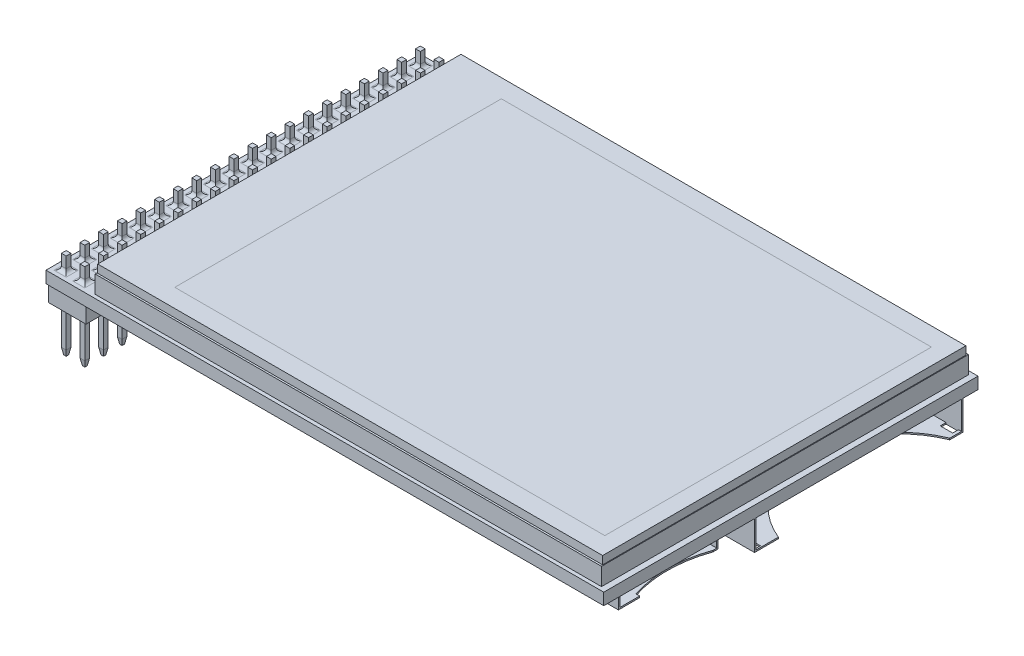
SolidWorks part; units mm, degrees
ref_plane "Спереди" through (0, 0, 0) normal (0, 0, 1) x (1, 0, 0)
ref_plane "Сверху" through (0, 0, 0) normal (0, 1, 0) x (1, 0, 0)
ref_plane "Справа" through (0, 0, 0) normal (1, 0, 0) x (0, 0, -1)
sketch "Эскиз10" plane through (0, 0, 0) normal (0, 1, 0) x (1, 0, 0)
  line L0 (278.9333, -1.3667) -> (1412.2667, -1.3667) construction
sketch "Эскиз1" plane through (0, 0, 0) normal (0, 1, 0) x (1, 0, 0)
  line L1 (0, -25.5) -> (76, -25.5)
  line L2 (0, -25.5) -> (0, 25.5)
  line L3 (0, 25.5) -> (76, 25.5)
  line L4 (76, -25.5) -> (76, 25.5)
  dimension "D1" = 51
  dimension "D2" = 76
extrude "Бобышка-Вытянуть1" add sketch "Эскиз1" along normal blind 1.6
sketch "Эскиз2" plane through (0, 0, 0) normal (0, -1, 0) x (1, 0, 0)
  line L0 (0, 0) -> (0.1, 0) construction
  line L1 (0.1, -25.25) -> (5.2, -25.25)
  line L2 (0.1, -25.25) -> (0.1, 25.25)
  line L3 (0.1, 25.25) -> (5.2, 25.25)
  line L4 (5.2, -25.25) -> (5.2, 25.25)
  dimension "D1" = 0.1
  dimension "D2" = 50.5
  dimension "D3" = 5.1
extrude "Бобышка-Вытянуть2" add sketch "Эскиз2" along normal blind 2.3
sketch "Эскиз3" plane through (0, -2.3, 0) normal (0, -1, 0) x (1, 0, 0)
  line L0 (1.38, -24.13) -> (1.38, -21.59) construction
  line L1 (1.38, -21.59) -> (1.38, -19.05) construction
  line L2 (1.38, -19.05) -> (1.38, -16.51) construction
  line L3 (1.38, -16.51) -> (1.38, -13.97) construction
  line L4 (1.38, -13.97) -> (1.38, -11.43) construction
  line L5 (1.38, -11.43) -> (1.38, -8.89) construction
  line L6 (1.38, -8.89) -> (1.38, -6.35) construction
  line L7 (1.38, -6.35) -> (1.38, -3.81) construction
  line L8 (1.38, -3.81) -> (1.38, -1.27) construction
  line L9 (1.38, -1.27) -> (1.38, 1.27) construction
  line L10 (1.38, 1.27) -> (1.38, 3.81) construction
  line L11 (1.38, 3.81) -> (1.38, 6.35) construction
  line L12 (1.38, 6.35) -> (1.38, 8.89) construction
  line L13 (1.38, 8.89) -> (1.38, 11.43) construction
  line L14 (1.38, 11.43) -> (1.38, 13.97) construction
  line L15 (1.38, 13.97) -> (1.38, 16.51) construction
  line L16 (1.38, 16.51) -> (1.38, 19.05) construction
  line L17 (1.38, 19.05) -> (1.38, 21.59) construction
  line L18 (1.38, 21.59) -> (1.38, 24.13) construction
  line L19 (1.38, 24.13) -> (3.92, 24.13) construction
  line L20 (3.92, 24.13) -> (3.92, 21.59) construction
  line L21 (3.92, 21.59) -> (1.38, 21.59) construction
  line L22 (3.92, 21.59) -> (3.92, 19.05) construction
  line L23 (3.92, 19.05) -> (1.38, 19.05) construction
  line L24 (3.92, 19.05) -> (3.92, 16.51) construction
  line L25 (3.92, 16.51) -> (1.38, 16.51) construction
  line L26 (3.92, 16.51) -> (3.92, 13.97) construction
  line L27 (3.92, 13.97) -> (1.38, 13.97) construction
  line L28 (3.92, 13.97) -> (3.92, 11.43) construction
  line L29 (3.92, 11.43) -> (1.38, 11.43) construction
  line L30 (3.92, 11.43) -> (3.92, 8.89) construction
  line L31 (3.92, 8.89) -> (1.38, 8.89) construction
  line L32 (3.92, 8.89) -> (3.92, 6.35) construction
  line L33 (3.92, 6.35) -> (1.38, 6.35) construction
  line L34 (3.92, 6.35) -> (3.92, 3.81) construction
  line L35 (3.92, 3.81) -> (1.38, 3.81) construction
  line L36 (3.92, 3.81) -> (3.92, 1.27) construction
  line L37 (3.92, 1.27) -> (1.38, 1.27) construction
  line L38 (3.92, 1.27) -> (3.92, -1.27) construction
  line L39 (3.92, -1.27) -> (1.38, -1.27) construction
  line L40 (3.92, -1.27) -> (3.92, -3.81) construction
  line L41 (3.92, -3.81) -> (1.38, -3.81) construction
  line L42 (3.92, -3.81) -> (3.92, -6.35) construction
  line L43 (3.92, -6.35) -> (1.38, -6.35) construction
  line L44 (3.92, -6.35) -> (3.92, -8.89) construction
  line L45 (3.92, -8.89) -> (1.38, -8.89) construction
  line L46 (3.92, -8.89) -> (3.92, -11.43) construction
  line L47 (3.92, -11.43) -> (1.38, -11.43) construction
  line L48 (3.92, -11.43) -> (3.92, -13.97) construction
  line L49 (3.92, -13.97) -> (1.38, -13.97) construction
  line L50 (3.92, -13.97) -> (3.92, -16.51) construction
  line L51 (3.92, -16.51) -> (1.38, -16.51) construction
  line L52 (3.92, -16.51) -> (3.92, -19.05) construction
  line L53 (3.92, -19.05) -> (1.38, -19.05) construction
  line L54 (3.92, -19.05) -> (3.92, -21.59) construction
  line L55 (3.92, -21.59) -> (1.38, -21.59) construction
  line L56 (3.92, -21.59) -> (3.92, -24.13) construction
  line L57 (3.92, -24.13) -> (1.38, -24.13) construction
  line L58 (1.38, 0) -> (0.1, 0) construction
  line L59 (0.1, 25.25) -> (0.1, -25.25) construction
  line L60 (2.65, 25.25) -> (2.65, 24.13) construction
  line L61 (5.2, 25.25) -> (0.1, 25.25) construction
  line L62 (1.705, 23.805) -> (1.055, 24.455) construction
  line L63 (1.055, 24.455) -> (1.705, 24.455)
  line L64 (1.055, 24.455) -> (1.055, 23.805)
  line L65 (1.055, 23.805) -> (1.705, 23.805)
  line L66 (1.705, 24.455) -> (1.705, 23.805)
  line L67 (1.055, 21.915) -> (1.705, 21.915)
  line L68 (1.055, 21.915) -> (1.055, 21.265)
  line L69 (1.055, 21.265) -> (1.705, 21.265)
  line L70 (1.705, 21.915) -> (1.705, 21.265)
  line L71 (1.055, 21.915) -> (1.705, 21.265) construction
  line L72 (1.055, 19.375) -> (1.705, 18.725) construction
  line L73 (1.055, 1.595) -> (1.705, 0.945) construction
  line L74 (1.055, 1.595) -> (1.705, 1.595)
  line L75 (1.055, 1.595) -> (1.055, 0.945)
  line L76 (1.055, 0.945) -> (1.705, 0.945)
  line L77 (1.705, 1.595) -> (1.705, 0.945)
  line L78 (1.055, -0.945) -> (1.705, -1.595) construction
  line L79 (1.055, 16.835) -> (1.705, 16.185) construction
  line L80 (1.055, 4.135) -> (1.705, 4.135)
  line L81 (1.055, 4.135) -> (1.055, 3.485)
  line L82 (1.055, 3.485) -> (1.705, 3.485)
  line L83 (1.705, 4.135) -> (1.705, 3.485)
  line L84 (1.055, 6.675) -> (1.705, 6.675)
  line L85 (1.055, 6.675) -> (1.055, 6.025)
  line L86 (1.055, 6.025) -> (1.705, 6.025)
  line L87 (1.705, 6.675) -> (1.705, 6.025)
  line L88 (1.055, 9.215) -> (1.705, 9.215)
  line L89 (1.055, 9.215) -> (1.055, 8.565)
  line L90 (1.055, 8.565) -> (1.705, 8.565)
  line L91 (1.705, 9.215) -> (1.705, 8.565)
  line L92 (1.055, 11.755) -> (1.705, 11.755)
  line L93 (1.055, 11.755) -> (1.055, 11.105)
  line L94 (1.055, 11.105) -> (1.705, 11.105)
  line L95 (1.705, 11.755) -> (1.705, 11.105)
  line L96 (1.055, 14.295) -> (1.705, 14.295)
  line L97 (1.055, 14.295) -> (1.055, 13.645)
  line L98 (1.055, 13.645) -> (1.705, 13.645)
  line L99 (1.705, 14.295) -> (1.705, 13.645)
  line L100 (1.055, 16.835) -> (1.705, 16.835)
  line L101 (1.055, 16.835) -> (1.055, 16.185)
  line L102 (1.055, 16.185) -> (1.705, 16.185)
  line L103 (1.705, 16.835) -> (1.705, 16.185)
  line L104 (1.055, 19.375) -> (1.705, 19.375)
  line L105 (1.055, 19.375) -> (1.055, 18.725)
  line L106 (1.055, 18.725) -> (1.705, 18.725)
  line L107 (1.705, 19.375) -> (1.705, 18.725)
  line L108 (1.055, 14.295) -> (1.705, 13.645) construction
  line L109 (1.055, 11.755) -> (1.705, 11.105) construction
  line L110 (1.055, -0.945) -> (1.705, -0.945)
  line L111 (1.055, 9.215) -> (1.705, 8.565) construction
  line L112 (1.055, 6.675) -> (1.705, 6.025) construction
  line L113 (1.055, 4.135) -> (1.705, 3.485) construction
  line L114 (1.055, -0.945) -> (1.055, -1.595)
  line L115 (1.055, -1.595) -> (1.705, -1.595)
  line L116 (1.705, -0.945) -> (1.705, -1.595)
  line L117 (1.055, -3.485) -> (1.705, -3.485)
  line L118 (1.055, -3.485) -> (1.055, -4.135)
  line L119 (1.055, -4.135) -> (1.705, -4.135)
  line L120 (1.705, -3.485) -> (1.705, -4.135)
  line L121 (1.055, -6.025) -> (1.705, -6.025)
  line L122 (1.055, -6.025) -> (1.055, -6.675)
  line L123 (1.055, -6.675) -> (1.705, -6.675)
  line L124 (1.705, -6.025) -> (1.705, -6.675)
  line L125 (1.055, -8.565) -> (1.705, -8.565)
  line L126 (1.055, -8.565) -> (1.055, -9.215)
  line L127 (1.055, -9.215) -> (1.705, -9.215)
  line L128 (1.705, -8.565) -> (1.705, -9.215)
  line L129 (1.055, -11.105) -> (1.705, -11.105)
  line L130 (1.055, -11.105) -> (1.055, -11.755)
  line L131 (1.055, -11.755) -> (1.705, -11.755)
  line L132 (1.705, -11.105) -> (1.705, -11.755)
  line L133 (1.055, -13.645) -> (1.705, -13.645)
  line L134 (1.055, -13.645) -> (1.055, -14.295)
  line L135 (1.055, -14.295) -> (1.705, -14.295)
  line L136 (1.705, -13.645) -> (1.705, -14.295)
  line L137 (1.055, -16.185) -> (1.705, -16.185)
  line L138 (1.055, -16.185) -> (1.055, -16.835)
  line L139 (1.055, -16.835) -> (1.705, -16.835)
  line L140 (1.705, -16.185) -> (1.705, -16.835)
  line L141 (1.055, -18.725) -> (1.705, -18.725)
  line L142 (1.055, -18.725) -> (1.055, -19.375)
  line L143 (1.055, -19.375) -> (1.705, -19.375)
  line L144 (1.705, -18.725) -> (1.705, -19.375)
  line L145 (1.055, -21.265) -> (1.705, -21.265)
  line L146 (1.055, -21.265) -> (1.055, -21.915)
  line L147 (1.055, -21.915) -> (1.705, -21.915)
  line L148 (1.705, -21.265) -> (1.705, -21.915)
  line L149 (1.055, -23.805) -> (1.705, -23.805)
  line L150 (1.055, -23.805) -> (1.055, -24.455)
  line L151 (1.055, -24.455) -> (1.705, -24.455)
  line L152 (1.705, -23.805) -> (1.705, -24.455)
  line L153 (1.055, -3.485) -> (1.705, -4.135) construction
  line L154 (1.055, -6.025) -> (1.705, -6.675) construction
  line L155 (1.055, -8.565) -> (1.705, -9.215) construction
  line L156 (1.055, -11.105) -> (1.705, -11.755) construction
  line L157 (1.055, -13.645) -> (1.705, -14.295) construction
  line L158 (1.055, -16.185) -> (1.705, -16.835) construction
  line L159 (1.055, -18.725) -> (1.705, -19.375) construction
  line L160 (1.055, -21.265) -> (1.705, -21.915) construction
  line L161 (1.055, -23.805) -> (1.705, -24.455) construction
  line L162 (3.595, 23.805) -> (4.245, 24.455) construction
  line L163 (3.595, 24.455) -> (4.245, 24.455)
  line L164 (3.595, 24.455) -> (3.595, 23.805)
  line L165 (3.595, 23.805) -> (4.245, 23.805)
  line L166 (4.245, 24.455) -> (4.245, 23.805)
  line L167 (3.595, 21.265) -> (4.245, 21.915) construction
  line L168 (3.595, 21.915) -> (4.245, 21.915)
  line L169 (3.595, 21.915) -> (3.595, 21.265)
  line L170 (3.595, 21.265) -> (4.245, 21.265)
  line L171 (4.245, 21.915) -> (4.245, 21.265)
  line L172 (3.595, 18.725) -> (4.245, 19.375) construction
  line L173 (3.595, 18.725) -> (4.245, 18.725)
  line L174 (3.595, 18.725) -> (3.595, 19.375)
  line L175 (3.595, 19.375) -> (4.245, 19.375)
  line L176 (4.245, 18.725) -> (4.245, 19.375)
  line L177 (3.595, 16.835) -> (4.245, 16.835)
  line L178 (3.595, 16.835) -> (3.595, 16.185)
  line L179 (3.595, 16.185) -> (4.245, 16.185)
  line L180 (4.245, 16.835) -> (4.245, 16.185)
  line L181 (3.595, 14.295) -> (4.245, 14.295)
  line L182 (3.595, 14.295) -> (3.595, 13.645)
  line L183 (3.595, 13.645) -> (4.245, 13.645)
  line L184 (4.245, 14.295) -> (4.245, 13.645)
  line L185 (3.595, 11.755) -> (4.245, 11.755)
  line L186 (3.595, 11.755) -> (3.595, 11.105)
  line L187 (3.595, 11.105) -> (4.245, 11.105)
  line L188 (4.245, 11.755) -> (4.245, 11.105)
  line L189 (3.595, 9.215) -> (4.245, 9.215)
  line L190 (3.595, 9.215) -> (3.595, 8.565)
  line L191 (3.595, 8.565) -> (4.245, 8.565)
  line L192 (4.245, 9.215) -> (4.245, 8.565)
  line L193 (3.595, 6.675) -> (4.245, 6.675)
  line L194 (3.595, 6.675) -> (3.595, 6.025)
  line L195 (3.595, 6.025) -> (4.245, 6.025)
  line L196 (4.245, 6.675) -> (4.245, 6.025)
  line L197 (3.595, 4.135) -> (4.245, 4.135)
  line L198 (3.595, 4.135) -> (3.595, 3.485)
  line L199 (3.595, 3.485) -> (4.245, 3.485)
  line L200 (4.245, 4.135) -> (4.245, 3.485)
  line L201 (3.595, 1.595) -> (4.245, 1.595)
  line L202 (3.595, 1.595) -> (3.595, 0.945)
  line L203 (3.595, 0.945) -> (4.245, 0.945)
  line L204 (4.245, 1.595) -> (4.245, 0.945)
  line L205 (3.595, -0.945) -> (4.245, -0.945)
  line L206 (3.595, -0.945) -> (3.595, -1.595)
  line L207 (3.595, -1.595) -> (4.245, -1.595)
  line L208 (4.245, -0.945) -> (4.245, -1.595)
  line L209 (3.595, -3.485) -> (4.245, -3.485)
  line L210 (3.595, -3.485) -> (3.595, -4.135)
  line L211 (3.595, -4.135) -> (4.245, -4.135)
  line L212 (4.245, -3.485) -> (4.245, -4.135)
  line L213 (3.595, -6.025) -> (4.245, -6.025)
  line L214 (3.595, -6.025) -> (3.595, -6.675)
  line L215 (3.595, -6.675) -> (4.245, -6.675)
  line L216 (4.245, -6.025) -> (4.245, -6.675)
  line L217 (3.595, -8.565) -> (4.245, -8.565)
  line L218 (3.595, -8.565) -> (3.595, -9.215)
  line L219 (3.595, -9.215) -> (4.245, -9.215)
  line L220 (4.245, -8.565) -> (4.245, -9.215)
  line L221 (3.595, -11.105) -> (4.245, -11.105)
  line L222 (3.595, -11.105) -> (3.595, -11.755)
  line L223 (3.595, -11.755) -> (4.245, -11.755)
  line L224 (4.245, -11.105) -> (4.245, -11.755)
  line L225 (3.595, -13.645) -> (4.245, -13.645)
  line L226 (3.595, -13.645) -> (3.595, -14.295)
  line L227 (3.595, -14.295) -> (4.245, -14.295)
  line L228 (4.245, -13.645) -> (4.245, -14.295)
  line L229 (3.595, -16.185) -> (4.245, -16.185)
  line L230 (3.595, -16.185) -> (3.595, -16.835)
  line L231 (3.595, -16.835) -> (4.245, -16.835)
  line L232 (4.245, -16.185) -> (4.245, -16.835)
  line L233 (3.595, -18.725) -> (4.245, -18.725)
  line L234 (3.595, -18.725) -> (3.595, -19.375)
  line L235 (3.595, -19.375) -> (4.245, -19.375)
  line L236 (4.245, -18.725) -> (4.245, -19.375)
  line L237 (3.595, -21.265) -> (4.245, -21.265)
  line L238 (3.595, -21.265) -> (3.595, -21.915)
  line L239 (3.595, -21.915) -> (4.245, -21.915)
  line L240 (4.245, -21.265) -> (4.245, -21.915)
  line L241 (3.595, -23.805) -> (4.245, -23.805)
  line L242 (3.595, -23.805) -> (3.595, -24.455)
  line L243 (3.595, -24.455) -> (4.245, -24.455)
  line L244 (4.245, -23.805) -> (4.245, -24.455)
  line L245 (3.595, 16.185) -> (4.245, 16.835) construction
  line L246 (3.595, -4.135) -> (4.245, -3.485) construction
  line L247 (3.595, 13.645) -> (4.245, 14.295) construction
  line L248 (3.595, 11.105) -> (4.245, 11.755) construction
  line L249 (3.595, 8.565) -> (4.245, 9.215) construction
  line L250 (3.595, 6.025) -> (4.245, 6.675) construction
  line L251 (3.595, 3.485) -> (4.245, 4.135) construction
  line L252 (3.595, 0.945) -> (4.245, 1.595) construction
  line L253 (3.595, -1.595) -> (4.245, -0.945) construction
  line L254 (3.595, -6.675) -> (4.245, -6.025) construction
  line L255 (3.595, -9.215) -> (4.245, -8.565) construction
  line L256 (3.595, -11.755) -> (4.245, -11.105) construction
  line L257 (3.595, -14.295) -> (4.245, -13.645) construction
  line L258 (3.595, -16.835) -> (4.245, -16.185) construction
  line L259 (3.595, -19.375) -> (4.245, -18.725) construction
  line L260 (3.595, -21.915) -> (4.245, -21.265) construction
  line L261 (3.595, -24.455) -> (4.245, -23.805) construction
  dimension "D1" = 2.54
  dimension "D2" = 2.54
  dimension "D3" = 0.65
extrude "Бобышка-Вытянуть3" add sketch "Эскиз3" along normal blind 6.1
sketch "Эскиз4" plane through (0, 1.6, 0) normal (0, 1, 0) x (1, 0, 0)
  line L1 (1.055, 23.805) -> (1.705, 23.805)
  line L2 (1.055, 23.805) -> (1.055, 24.455)
  line L3 (1.055, 24.455) -> (1.705, 24.455)
  line L4 (1.705, 23.805) -> (1.705, 24.455)
  line L5 (3.595, 24.455) -> (4.245, 24.455)
  line L6 (3.595, 24.455) -> (3.595, 23.805)
  line L7 (3.595, 23.805) -> (4.245, 23.805)
  line L8 (4.245, 24.455) -> (4.245, 23.805)
  line L9 (1.055, 21.915) -> (1.705, 21.915)
  line L10 (1.055, 21.915) -> (1.055, 21.265)
  line L11 (1.055, 21.265) -> (1.705, 21.265)
  line L12 (1.705, 21.915) -> (1.705, 21.265)
  line L13 (3.595, 21.915) -> (4.245, 21.915)
  line L14 (3.595, 21.915) -> (3.595, 21.265)
  line L15 (3.595, 21.265) -> (4.245, 21.265)
  line L16 (4.245, 21.915) -> (4.245, 21.265)
  line L17 (1.055, 19.375) -> (1.705, 19.375)
  line L18 (1.055, 19.375) -> (1.055, 18.725)
  line L19 (1.055, 18.725) -> (1.705, 18.725)
  line L20 (1.705, 19.375) -> (1.705, 18.725)
  line L21 (3.595, 19.375) -> (4.245, 19.375)
  line L22 (3.595, 19.375) -> (3.595, 18.725)
  line L23 (3.595, 18.725) -> (4.245, 18.725)
  line L24 (4.245, 19.375) -> (4.245, 18.725)
  line L25 (1.055, 16.835) -> (1.705, 16.835)
  line L26 (1.055, 16.835) -> (1.055, 16.185)
  line L27 (1.055, 16.185) -> (1.705, 16.185)
  line L28 (1.705, 16.835) -> (1.705, 16.185)
  line L29 (3.595, 16.835) -> (4.245, 16.835)
  line L30 (3.595, 16.835) -> (3.595, 16.185)
  line L31 (3.595, 16.185) -> (4.245, 16.185)
  line L32 (4.245, 16.835) -> (4.245, 16.185)
  line L33 (1.055, 14.295) -> (1.705, 14.295)
  line L34 (1.055, 14.295) -> (1.055, 13.645)
  line L35 (1.055, 13.645) -> (1.705, 13.645)
  line L36 (1.705, 14.295) -> (1.705, 13.645)
  line L37 (3.595, 14.295) -> (4.245, 14.295)
  line L38 (3.595, 14.295) -> (3.595, 13.645)
  line L39 (3.595, 13.645) -> (4.245, 13.645)
  line L40 (4.245, 14.295) -> (4.245, 13.645)
  line L41 (1.055, 11.755) -> (1.705, 11.755)
  line L42 (1.055, 11.755) -> (1.055, 11.105)
  line L43 (1.055, 11.105) -> (1.705, 11.105)
  line L44 (1.705, 11.755) -> (1.705, 11.105)
  line L45 (3.595, 11.755) -> (4.245, 11.755)
  line L46 (3.595, 11.755) -> (3.595, 11.105)
  line L47 (3.595, 11.105) -> (4.245, 11.105)
  line L48 (4.245, 11.755) -> (4.245, 11.105)
  line L49 (1.055, 9.215) -> (1.705, 9.215)
  line L50 (1.055, 9.215) -> (1.055, 8.565)
  line L51 (1.055, 8.565) -> (1.705, 8.565)
  line L52 (1.705, 9.215) -> (1.705, 8.565)
  line L53 (3.595, 9.215) -> (4.245, 9.215)
  line L54 (3.595, 9.215) -> (3.595, 8.565)
  line L55 (3.595, 8.565) -> (4.245, 8.565)
  line L56 (4.245, 9.215) -> (4.245, 8.565)
  line L57 (1.055, 6.675) -> (1.705, 6.675)
  line L58 (1.055, 6.675) -> (1.055, 6.025)
  line L59 (1.055, 6.025) -> (1.705, 6.025)
  line L60 (1.705, 6.675) -> (1.705, 6.025)
  line L61 (3.595, 6.675) -> (4.245, 6.675)
  line L62 (3.595, 6.675) -> (3.595, 6.025)
  line L63 (3.595, 6.025) -> (4.245, 6.025)
  line L64 (4.245, 6.675) -> (4.245, 6.025)
  line L65 (1.055, 4.135) -> (1.705, 4.135)
  line L66 (1.055, 4.135) -> (1.055, 3.485)
  line L67 (1.055, 3.485) -> (1.705, 3.485)
  line L68 (1.705, 4.135) -> (1.705, 3.485)
  line L69 (3.595, 4.135) -> (4.245, 4.135)
  line L70 (3.595, 4.135) -> (3.595, 3.485)
  line L71 (3.595, 3.485) -> (4.245, 3.485)
  line L72 (4.245, 4.135) -> (4.245, 3.485)
  line L73 (1.055, 1.595) -> (1.705, 1.595)
  line L74 (1.055, 1.595) -> (1.055, 0.945)
  line L75 (1.055, 0.945) -> (1.705, 0.945)
  line L76 (1.705, 1.595) -> (1.705, 0.945)
  line L77 (3.595, 1.595) -> (4.245, 1.595)
  line L78 (3.595, 1.595) -> (3.595, 0.945)
  line L79 (3.595, 0.945) -> (4.245, 0.945)
  line L80 (4.245, 1.595) -> (4.245, 0.945)
  line L81 (1.055, -0.945) -> (1.705, -0.945)
  line L82 (1.055, -0.945) -> (1.055, -1.595)
  line L83 (1.055, -1.595) -> (1.705, -1.595)
  line L84 (1.705, -0.945) -> (1.705, -1.595)
  line L85 (3.595, -0.945) -> (4.245, -0.945)
  line L86 (3.595, -0.945) -> (3.595, -1.595)
  line L87 (3.595, -1.595) -> (4.245, -1.595)
  line L88 (4.245, -0.945) -> (4.245, -1.595)
  line L89 (1.055, -3.485) -> (1.705, -3.485)
  line L90 (1.055, -3.485) -> (1.055, -4.135)
  line L91 (1.055, -4.135) -> (1.705, -4.135)
  line L92 (1.705, -3.485) -> (1.705, -4.135)
  line L93 (3.595, -3.485) -> (4.245, -3.485)
  line L94 (3.595, -3.485) -> (3.595, -4.135)
  line L95 (3.595, -4.135) -> (4.245, -4.135)
  line L96 (4.245, -3.485) -> (4.245, -4.135)
  line L97 (1.055, -6.025) -> (1.705, -6.025)
  line L98 (1.055, -6.025) -> (1.055, -6.675)
  line L99 (1.055, -6.675) -> (1.705, -6.675)
  line L100 (1.705, -6.025) -> (1.705, -6.675)
  line L101 (3.595, -6.025) -> (4.245, -6.025)
  line L102 (3.595, -6.025) -> (3.595, -6.675)
  line L103 (3.595, -6.675) -> (4.245, -6.675)
  line L104 (4.245, -6.025) -> (4.245, -6.675)
  line L105 (1.055, -8.565) -> (1.705, -8.565)
  line L106 (1.055, -8.565) -> (1.055, -9.215)
  line L107 (1.055, -9.215) -> (1.705, -9.215)
  line L108 (1.705, -8.565) -> (1.705, -9.215)
  line L109 (3.595, -8.565) -> (4.245, -8.565)
  line L110 (3.595, -8.565) -> (3.595, -9.215)
  line L111 (3.595, -9.215) -> (4.245, -9.215)
  line L112 (4.245, -8.565) -> (4.245, -9.215)
  line L113 (1.055, -11.105) -> (1.705, -11.105)
  line L114 (1.055, -11.105) -> (1.055, -11.755)
  line L115 (1.055, -11.755) -> (1.705, -11.755)
  line L116 (1.705, -11.105) -> (1.705, -11.755)
  line L117 (3.595, -11.105) -> (4.245, -11.105)
  line L118 (3.595, -11.105) -> (3.595, -11.755)
  line L119 (3.595, -11.755) -> (4.245, -11.755)
  line L120 (4.245, -11.105) -> (4.245, -11.755)
  line L121 (1.055, -13.645) -> (1.705, -13.645)
  line L122 (1.055, -13.645) -> (1.055, -14.295)
  line L123 (1.055, -14.295) -> (1.705, -14.295)
  line L124 (1.705, -13.645) -> (1.705, -14.295)
  line L125 (3.595, -13.645) -> (4.245, -13.645)
  line L126 (3.595, -13.645) -> (3.595, -14.295)
  line L127 (3.595, -14.295) -> (4.245, -14.295)
  line L128 (4.245, -13.645) -> (4.245, -14.295)
  line L129 (1.055, -16.185) -> (1.705, -16.185)
  line L130 (1.055, -16.185) -> (1.055, -16.835)
  line L131 (1.055, -16.835) -> (1.705, -16.835)
  line L132 (1.705, -16.185) -> (1.705, -16.835)
  line L133 (3.595, -16.185) -> (4.245, -16.185)
  line L134 (3.595, -16.185) -> (3.595, -16.835)
  line L135 (3.595, -16.835) -> (4.245, -16.835)
  line L136 (4.245, -16.185) -> (4.245, -16.835)
  line L137 (1.055, -18.725) -> (1.705, -18.725)
  line L138 (1.055, -18.725) -> (1.055, -19.375)
  line L139 (1.055, -19.375) -> (1.705, -19.375)
  line L140 (1.705, -18.725) -> (1.705, -19.375)
  line L141 (3.595, -18.725) -> (4.245, -18.725)
  line L142 (3.595, -18.725) -> (3.595, -19.375)
  line L143 (3.595, -19.375) -> (4.245, -19.375)
  line L144 (4.245, -18.725) -> (4.245, -19.375)
  line L145 (1.055, -21.265) -> (1.705, -21.265)
  line L146 (1.055, -21.265) -> (1.055, -21.915)
  line L147 (1.055, -21.915) -> (1.705, -21.915)
  line L148 (1.705, -21.265) -> (1.705, -21.915)
  line L149 (3.595, -21.265) -> (4.245, -21.265)
  line L150 (3.595, -21.265) -> (3.595, -21.915)
  line L151 (3.595, -21.915) -> (4.245, -21.915)
  line L152 (4.245, -21.265) -> (4.245, -21.915)
  line L153 (1.055, -23.805) -> (1.705, -23.805)
  line L154 (1.055, -23.805) -> (1.055, -24.455)
  line L155 (1.055, -24.455) -> (1.705, -24.455)
  line L156 (1.705, -23.805) -> (1.705, -24.455)
  line L157 (3.595, -23.805) -> (4.245, -23.805)
  line L158 (3.595, -23.805) -> (3.595, -24.455)
  line L159 (3.595, -24.455) -> (4.245, -24.455)
  line L160 (4.245, -23.805) -> (4.245, -24.455)
extrude "Бобышка-Вытянуть4" add sketch "Эскиз4" along normal blind 2
chamfer "Фаска1" distance 0.16 angle 80 160 edges at (3.92, -8.4, 24.455) (4.245, -8.4, 24.13) (3.92, -8.4, 23.805) (3.595, -8.4, 24.13) (3.92, -8.4, 21.915) (4.245, -8.4, 21.59) (3.92, -8.4, 21.265) (3.595, -8.4, 21.59) (3.92, -8.4, 19.375) (4.245, -8.4, 19.05) (3.92, -8.4, 18.725) (3.595, -8.4, 19.05) (3.92, -8.4, 16.835) (4.245, -8.4, 16.51) (3.92, -8.4, 16.185) (3.595, -8.4, 16.51) (3.92, -8.4, 14.295) (4.245, -8.4, 13.97) (3.92, -8.4, 13.645) (3.595, -8.4, 13.97) (3.92, -8.4, 11.755) (4.245, -8.4, 11.43) (3.92, -8.4, 11.105) (3.595, -8.4, 11.43) (3.92, -8.4, 9.215) (4.245, -8.4, 8.89) (3.92, -8.4, 8.565) (3.595, -8.4, 8.89) (3.92, -8.4, 6.675) (4.245, -8.4, 6.35) (3.92, -8.4, 6.025) (3.595, -8.4, 6.35) (3.92, -8.4, 4.135) (4.245, -8.4, 3.81) (3.92, -8.4, 3.485) (3.595, -8.4, 3.81) (3.92, -8.4, 1.595) (4.245, -8.4, 1.27) (3.92, -8.4, 0.945) (3.595, -8.4, 1.27) (3.92, -8.4, -0.945) (4.245, -8.4, -1.27) (3.92, -8.4, -1.595) (3.595, -8.4, -1.27) (3.92, -8.4, -3.485) (4.245, -8.4, -3.81) (3.92, -8.4, -4.135) (3.595, -8.4, -3.81) (3.92, -8.4, -6.025) (4.245, -8.4, -6.35) (3.92, -8.4, -6.675) (3.595, -8.4, -6.35) (3.92, -8.4, -8.565) (4.245, -8.4, -8.89) (3.92, -8.4, -9.215) (3.595, -8.4, -8.89) (3.92, -8.4, -11.105) (4.245, -8.4, -11.43) (3.92, -8.4, -11.755) (3.595, -8.4, -11.43) (3.92, -8.4, -13.645) (4.245, -8.4, -13.97) (3.92, -8.4, -14.295) (3.595, -8.4, -13.97) (3.92, -8.4, -16.185) (4.245, -8.4, -16.51) (3.92, -8.4, -16.835) (3.595, -8.4, -16.51) (3.92, -8.4, -18.725) (4.245, -8.4, -19.05) (3.92, -8.4, -19.375) (3.595, -8.4, -19.05) (3.92, -8.4, -21.265) (4.245, -8.4, -21.59) (3.92, -8.4, -21.915) (3.595, -8.4, -21.59) (3.92, -8.4, -23.805) (4.245, -8.4, -24.13) (3.92, -8.4, -24.455) (3.595, -8.4, -24.13) (1.38, -8.4, -23.805) (1.705, -8.4, -24.13) (1.38, -8.4, -24.455) (1.055, -8.4, -24.13) (1.38, -8.4, -21.265) (1.705, -8.4, -21.59) (1.38, -8.4, -21.915) (1.055, -8.4, -21.59) (1.38, -8.4, -18.725) (1.705, -8.4, -19.05) (1.38, -8.4, -19.375) (1.055, -8.4, -19.05) (1.38, -8.4, -16.185) (1.705, -8.4, -16.51) (1.38, -8.4, -16.835) (1.055, -8.4, -16.51) (1.38, -8.4, -13.645) (1.705, -8.4, -13.97) (1.38, -8.4, -14.295) (1.055, -8.4, -13.97) (1.38, -8.4, -11.105) (1.705, -8.4, -11.43) (1.38, -8.4, -11.755) (1.055, -8.4, -11.43) (1.38, -8.4, -8.565) (1.705, -8.4, -8.89) (1.38, -8.4, -9.215) (1.055, -8.4, -8.89) (1.38, -8.4, -6.025) (1.705, -8.4, -6.35) (1.38, -8.4, -6.675) (1.055, -8.4, -6.35) (1.38, -8.4, -3.485) (1.705, -8.4, -3.81) (1.38, -8.4, -4.135) (1.055, -8.4, -3.81) (1.38, -8.4, -0.945) (1.705, -8.4, -1.27) (1.38, -8.4, -1.595) (1.055, -8.4, -1.27) (1.38, -8.4, 1.595) (1.705, -8.4, 1.27) (1.38, -8.4, 0.945) (1.055, -8.4, 1.27) (1.38, -8.4, 4.135) (1.705, -8.4, 3.81) (1.38, -8.4, 3.485) (1.055, -8.4, 3.81) (1.38, -8.4, 6.675) (1.705, -8.4, 6.35) (1.38, -8.4, 6.025) (1.055, -8.4, 6.35) (1.38, -8.4, 9.215) (1.705, -8.4, 8.89) (1.38, -8.4, 8.565) (1.055, -8.4, 8.89) (1.38, -8.4, 11.755) (1.705, -8.4, 11.43) (1.38, -8.4, 11.105) (1.055, -8.4, 11.43) (1.38, -8.4, 14.295) (1.705, -8.4, 13.97) (1.38, -8.4, 13.645) (1.055, -8.4, 13.97) (1.38, -8.4, 16.835) (1.705, -8.4, 16.51) (1.38, -8.4, 16.185) (1.055, -8.4, 16.51) (1.38, -8.4, 19.375) (1.705, -8.4, 19.05) (1.38, -8.4, 18.725) (1.055, -8.4, 19.05) (1.38, -8.4, 21.915) (1.705, -8.4, 21.59) (1.38, -8.4, 21.265) (1.055, -8.4, 21.59) (1.38, -8.4, 24.455) (1.705, -8.4, 24.13) (1.38, -8.4, 23.805) (1.055, -8.4, 24.13)
fillet "Скругление1" radius 0.5 80 edges at (1.705, 1.6, -24.13) (1.38, 1.6, -23.805) (1.38, 1.6, 24.455) (1.38, 1.6, 21.265) (1.055, 1.6, 19.05) (1.38, 1.6, 16.835) (1.055, 1.6, 16.51) (1.38, 1.6, 14.295) (1.38, 1.6, 13.645) (1.705, 1.6, 11.43) (1.38, 1.6, 11.755) (1.38, 1.6, 11.105) (1.705, 1.6, 8.89) (1.055, 1.6, 8.89) (1.38, 1.6, 8.565) (1.055, 1.6, 6.35) (1.38, 1.6, 6.025) (1.705, 1.6, 3.81) (1.055, 1.6, 3.81) (1.38, 1.6, 3.485) (1.705, 1.6, 1.27) (1.38, 1.6, 1.595) (1.055, 1.6, 1.27) (1.38, 1.6, 0.945) (1.705, 1.6, -1.27) (1.38, 1.6, -1.595) (1.705, 1.6, -3.81) (1.055, 1.6, -3.81) (1.38, 1.6, -6.025) (1.055, 1.6, -6.35) (1.705, 1.6, -8.89) (1.38, 1.6, -8.565) (1.055, 1.6, -8.89) (1.38, 1.6, -9.215) (1.705, 1.6, -11.43) (1.38, 1.6, -11.105) (1.38, 1.6, -13.645) (1.38, 1.6, -14.295) (1.705, 1.6, -16.51) (1.38, 1.6, -16.185) (1.38, 1.6, -16.835) (1.705, 1.6, -19.05) (1.38, 1.6, -18.725) (1.055, 1.6, -19.05) (3.595, 1.6, 24.13) (3.92, 1.6, 23.805) (3.595, 1.6, 21.59) (3.92, 1.6, 21.265) (4.245, 1.6, 16.51) (3.595, 1.6, 16.51) (3.92, 1.6, 16.185) (4.245, 1.6, 13.97) (3.92, 1.6, 14.295) (3.595, 1.6, 13.97) (4.245, 1.6, 11.43) (3.595, 1.6, 11.43) (3.92, 1.6, 9.215) (3.92, 1.6, 8.565) (3.92, 1.6, 6.675) (4.245, 1.6, 3.81) (3.92, 1.6, 4.135) (3.595, 1.6, 3.81) (4.245, 1.6, 1.27) (3.92, 1.6, 0.945) (3.92, 1.6, -0.945) (3.92, 1.6, -1.595) (3.92, 1.6, -4.135) (3.595, 1.6, -6.35) (4.245, 1.6, -8.89) (3.92, 1.6, -8.565) (3.92, 1.6, -9.215) (3.92, 1.6, -11.755) (4.245, 1.6, -13.97) (3.92, 1.6, -13.645) (3.92, 1.6, -16.185) (3.92, 1.6, -16.835) (3.595, 1.6, -19.05) (3.92, 1.6, -21.915) (3.595, 1.6, -24.13) (3.92, 1.6, -24.455)
sketch "Эскиз5" plane through (0, 1.6, 0) normal (0, 1, 0) x (1, 0, 0)
  line L0 (0, 0) -> (6.2, 0) construction
  line L1 (6.2, -25) -> (75.2, -25)
  line L2 (6.2, -25) -> (6.2, 25)
  line L3 (6.2, 25) -> (75.2, 25)
  line L4 (75.2, -25) -> (75.2, 25)
  line L5 (76, -25.5) -> (76, 25.5) construction
  dimension "D1" = 50
  dimension "D2" = 69
  dimension "D3" = 0.8
extrude "Бобышка-Вытянуть5" add sketch "Эскиз5" along normal blind 2.4
sketch "Эскиз6" plane through (0, 4, 0) normal (0, 1, 0) x (1, 0, 0)
  line L0 (0, 0) -> (6.3, 0) construction
  line L1 (6.3, -24.75) -> (75.1, -24.75)
  line L2 (6.3, -24.75) -> (6.3, 24.75)
  line L3 (6.3, 24.75) -> (75.1, 24.75)
  line L4 (75.1, -24.75) -> (75.1, 24.75)
  line L5 (0, 25.5) -> (0, -25.5) construction
  line L6 (75.2, -25) -> (75.2, 25) construction
  dimension "D1" = 49.5
  dimension "D2" = 68.8
  dimension "D3" = 0.1
extrude "Бобышка-Вытянуть6" add sketch "Эскиз6" along normal blind 1.1
sketch "Эскиз7" plane through (0, 5.1, 0) normal (0, 1, 0) x (1, 0, 0)
  line L0 (0, 0) -> (14.3, 0) construction
  line L1 (0, 25.5) -> (0, -25.5) construction
  line L2 (6.3, 24.75) -> (6.3, -24.75) construction
  line L3 (14.3, -22.25) -> (72.9, -22.25)
  line L4 (14.3, -22.25) -> (14.3, 22.25)
  line L5 (14.3, 22.25) -> (72.9, 22.25)
  line L6 (72.9, -22.25) -> (72.9, 22.25)
  dimension "D1" = 58.6
  dimension "D2" = 44.5
  dimension "D3" = 8
split line "Разделяющая линия1"
sketch "Эскиз11" plane through (0, 0, 0) normal (0, -1, 0) x (1, 0, 0)
  line L1 (14.8, -17.9) -> (18.4, -17.9)
  line L2 (14.8, -17.9) -> (14.8, -11.3)
  line L3 (14.8, -11.3) -> (18.4, -11.3)
  line L4 (18.4, -17.9) -> (18.4, -11.3)
  line L5 (16.1, 0.2) -> (19.9, 0.2)
  line L6 (16.1, 0.2) -> (16.1, 6.3)
  line L7 (16.1, 6.3) -> (19.9, 6.3)
  line L8 (19.9, 0.2) -> (19.9, 6.3)
  dimension "D1" = 3.6
  dimension "D2" = 6.6
  dimension "D3" = 14.8
  dimension "D4" = 11.3
  dimension "D5" = 0.2
  dimension "D6" = 6.1
  dimension "D7" = 16.1
  dimension "D8" = 3.8
extrude "Бобышка-Вытянуть7" add sketch "Эскиз11" along normal blind 1
sketch "Эскиз12" plane through (0, 0, 0) normal (0, -1, 0) x (1, 0, 0)
  line L0 (14.8, -11.3) -> (14.8, -17.9) construction
  line L1 (14.8, -17.6) -> (12.2, -17.6)
  line L2 (14.8, -17.6) -> (14.8, -16.4)
  line L3 (14.8, -16.4) -> (12.2, -16.4)
  line L4 (12.2, -17.6) -> (12.2, -16.4)
  line L5 (14.8, -11.3) -> (14.8, -17.9) construction
  line L6 (14.8, -14) -> (12.2, -14)
  line L7 (14.8, -14) -> (14.8, -15.2)
  line L8 (14.8, -15.2) -> (12.2, -15.2)
  line L9 (12.2, -14) -> (12.2, -15.2)
  line L10 (12.2, -12.8) -> (12.2, -14) construction
  line L11 (14.8, -12.8) -> (12.2, -12.8)
  line L12 (14.8, -12.8) -> (14.8, -11.6)
  line L13 (14.8, -11.6) -> (12.2, -11.6)
  line L14 (12.2, -12.8) -> (12.2, -11.6)
  line L15 (12.2, -15.2) -> (12.2, -16.4) construction
  line L16 (18.4, -17.9) -> (18.4, -11.3) construction
  line L17 (18.4, -16.4) -> (20.9, -16.4)
  line L18 (18.4, -16.4) -> (18.4, -12.8)
  line L19 (18.4, -12.8) -> (20.9, -12.8)
  line L20 (20.9, -16.4) -> (20.9, -12.8)
  line L21 (18.4, -17.9) -> (18.4, -11.3) construction
  line L22 (16.1, 6.3) -> (16.1, 0.2) construction
  line L23 (14, 0.775) -> (16.1, 0.775)
  line L24 (14, 0.775) -> (14, 1.175)
  line L25 (14, 1.175) -> (16.1, 1.175)
  line L26 (16.1, 0.775) -> (16.1, 1.175)
  line L27 (16.1, 6.3) -> (16.1, 0.2) construction
  line L28 (14, 1.425) -> (16.1, 1.425)
  line L29 (14, 1.425) -> (14, 1.825)
  line L30 (14, 1.825) -> (16.1, 1.825)
  line L31 (16.1, 1.425) -> (16.1, 1.825)
  line L32 (14, 1.175) -> (14, 1.425) construction
  line L33 (14, 2.075) -> (16.1, 2.075)
  line L34 (14, 2.075) -> (14, 2.475)
  line L35 (14, 2.475) -> (16.1, 2.475)
  line L36 (16.1, 2.075) -> (16.1, 2.475)
  line L37 (14, 2.725) -> (16.1, 2.725)
  line L38 (14, 2.725) -> (14, 3.125)
  line L39 (14, 3.125) -> (16.1, 3.125)
  line L40 (16.1, 2.725) -> (16.1, 3.125)
  line L41 (14, 3.375) -> (16.1, 3.375)
  line L42 (14, 3.375) -> (14, 3.775)
  line L43 (14, 3.775) -> (16.1, 3.775)
  line L44 (16.1, 3.375) -> (16.1, 3.775)
  line L45 (14, 4.025) -> (16.1, 4.025)
  line L46 (14, 4.025) -> (14, 4.425)
  line L47 (14, 4.425) -> (16.1, 4.425)
  line L48 (16.1, 4.025) -> (16.1, 4.425)
  line L49 (14, 4.675) -> (16.1, 4.675)
  line L50 (14, 4.675) -> (14, 5.075)
  line L51 (14, 5.075) -> (16.1, 5.075)
  line L52 (16.1, 4.675) -> (16.1, 5.075)
  line L53 (14, 5.325) -> (16.1, 5.325)
  line L54 (14, 5.325) -> (14, 5.725)
  line L55 (14, 5.725) -> (16.1, 5.725)
  line L56 (16.1, 5.325) -> (16.1, 5.725)
  line L57 (14, 1.825) -> (14, 2.075) construction
  line L58 (14, 2.475) -> (14, 2.725) construction
  line L59 (14, 3.125) -> (14, 3.375) construction
  line L60 (14, 3.775) -> (14, 4.025) construction
  line L61 (14, 4.425) -> (14, 4.675) construction
  line L62 (14, 5.075) -> (14, 5.325) construction
  line L63 (14, 3.25) -> (16.1, 3.25) construction
  line L64 (19.9, 0.2) -> (19.9, 6.3) construction
  line L67 (19.9, 5.725) -> (22, 5.725)
  line L68 (19.9, 5.725) -> (19.9, 5.325)
  line L69 (19.9, 5.325) -> (22, 5.325)
  line L70 (22, 5.725) -> (22, 5.325)
  line L71 (22, 5.325) -> (22, 5.075) construction
  line L72 (19.9, 5.075) -> (22, 5.075)
  line L73 (19.9, 5.075) -> (19.9, 4.675)
  line L74 (19.9, 4.675) -> (22, 4.675)
  line L75 (22, 5.075) -> (22, 4.675)
  line L76 (19.9, 4.425) -> (22, 4.425)
  line L77 (19.9, 4.425) -> (19.9, 4.025)
  line L78 (19.9, 4.025) -> (22, 4.025)
  line L79 (22, 4.425) -> (22, 4.025)
  line L80 (19.9, 3.775) -> (22, 3.775)
  line L81 (19.9, 3.775) -> (19.9, 3.375)
  line L82 (19.9, 3.375) -> (22, 3.375)
  line L83 (22, 3.775) -> (22, 3.375)
  line L84 (19.9, 3.125) -> (22, 3.125)
  line L85 (19.9, 3.125) -> (19.9, 2.725)
  line L86 (19.9, 2.725) -> (22, 2.725)
  line L87 (22, 3.125) -> (22, 2.725)
  line L88 (19.9, 2.475) -> (22, 2.475)
  line L89 (19.9, 2.475) -> (19.9, 2.075)
  line L90 (19.9, 2.075) -> (22, 2.075)
  line L91 (22, 2.475) -> (22, 2.075)
  line L92 (19.9, 1.825) -> (22, 1.825)
  line L93 (19.9, 1.825) -> (19.9, 1.425)
  line L94 (19.9, 1.425) -> (22, 1.425)
  line L95 (22, 1.825) -> (22, 1.425)
  line L96 (19.9, 1.175) -> (22, 1.175)
  line L97 (19.9, 1.175) -> (19.9, 0.775)
  line L98 (19.9, 0.775) -> (22, 0.775)
  line L99 (22, 1.175) -> (22, 0.775)
  line L100 (22, 4.675) -> (22, 4.425) construction
  line L101 (22, 4.025) -> (22, 3.775) construction
  line L102 (22, 3.375) -> (22, 3.125) construction
  line L103 (22, 2.725) -> (22, 2.475) construction
  line L104 (22, 2.075) -> (22, 1.825) construction
  line L105 (22, 1.425) -> (22, 1.175) construction
  line L106 (22, 3.25) -> (19.9, 3.25) construction
  line L107 (19.9, 0.2) -> (19.9, 6.3) construction
  point P18 (14.8, -14.6)
  point P23 (18.4, -14.6)
  dimension "D1" = 1.2
  dimension "D2" = 1.2
  dimension "D3" = 2.6
  dimension "D4" = 3.6
  dimension "D5" = 2.5
  dimension "D6" = 0.25
  dimension "D7" = 0.4
  dimension "D8" = 2.1
extrude "Бобышка-Вытянуть8" add sketch "Эскиз12" along normal blind 0.25
sketch "Эскиз13" plane through (0, 0, 0) normal (0, -1, 0) x (1, 0, 0)
  line L0 (12.95, -20.3) -> (14.55, -20.3) construction
  line L1 (12.35, -19.65) -> (12.95, -19.65)
  line L2 (12.35, -19.65) -> (12.35, -20.95)
  line L3 (12.35, -20.95) -> (12.95, -20.95)
  line L4 (12.95, -19.65) -> (12.95, -20.95)
  line L5 (14.55, -20.95) -> (15.15, -20.95)
  line L6 (14.55, -20.95) -> (14.55, -19.65)
  line L7 (14.55, -19.65) -> (15.15, -19.65)
  line L8 (15.15, -20.95) -> (15.15, -19.65)
  line L9 (15, -1.65) -> (16.6, -1.65) construction
  line L10 (14.4, -2.3) -> (15, -2.3)
  line L11 (14.4, -2.3) -> (14.4, -1)
  line L12 (14.4, -1) -> (15, -1)
  line L13 (15, -2.3) -> (15, -1)
  line L14 (16.6, -2.3) -> (17.2, -2.3)
  line L15 (16.6, -2.3) -> (16.6, -1)
  line L16 (16.6, -1) -> (17.2, -1)
  line L17 (17.2, -2.3) -> (17.2, -1)
  line L18 (19.75, -1.65) -> (21.35, -1.65) construction
  line L19 (19.15, -2.3) -> (19.75, -2.3)
  line L20 (19.15, -2.3) -> (19.15, -1)
  line L21 (19.15, -1) -> (19.75, -1)
  line L22 (19.75, -2.3) -> (19.75, -1)
  line L23 (21.35, -2.3) -> (21.95, -2.3)
  line L24 (21.35, -2.3) -> (21.35, -1)
  line L25 (21.35, -1) -> (21.95, -1)
  line L26 (21.95, -2.3) -> (21.95, -1)
  line L27 (25.9, 5) -> (25.9, 3.4) construction
  line L28 (25.25, 2.8) -> (26.55, 2.8)
  line L29 (25.25, 2.8) -> (25.25, 3.4)
  line L30 (25.25, 3.4) -> (26.55, 3.4)
  line L31 (26.55, 2.8) -> (26.55, 3.4)
  line L32 (25.25, 5) -> (26.55, 5)
  line L33 (25.25, 5) -> (25.25, 5.6)
  line L34 (25.25, 5.6) -> (26.55, 5.6)
  line L35 (26.55, 5) -> (26.55, 5.6)
  point P11 (13.75, -20.3)
  point P22 (15.8, -1.65)
  point P33 (20.55, -1.65)
  point P44 (25.9, 4.2)
  dimension "D1" = 1.3
  dimension "D2" = 0.6
  dimension "D3" = 1.6
  dimension "D4" = 13.75
  dimension "D5" = 20.3
  dimension "D6" = 0.6
  dimension "D7" = 1.6
  dimension "D8" = 1.3
  dimension "D9" = 1.65
  dimension "D10" = 15.8
  dimension "D11" = 4.75
  dimension "D12" = 4.2
  dimension "D13" = 25.9
extrude "Бобышка-Вытянуть9" add sketch "Эскиз13" along normal blind 1
sketch "Эскиз14" plane through (0, 0, 0) normal (0, -1, 0) x (1, 0, 0)
  line L0 (12.95, -20.95) -> (12.95, -19.65) construction
  line L1 (12.95, -20.95) -> (12.95, -19.65) construction
  line L2 (12.95, -20.85) -> (14.55, -20.85)
  line L3 (12.95, -20.85) -> (12.95, -19.75)
  line L4 (12.95, -19.75) -> (14.55, -19.75)
  line L5 (14.55, -20.85) -> (14.55, -19.75)
  line L6 (14.55, -19.65) -> (14.55, -20.95) construction
  line L7 (15, -2.3) -> (15, -1) construction
  line L8 (19.75, -2.3) -> (19.75, -1) construction
  line L9 (26.55, 3.4) -> (25.25, 3.4) construction
  line L10 (16.6, -1) -> (16.6, -2.3) construction
  line L11 (15, -2.2) -> (16.6, -2.2)
  line L12 (15, -2.2) -> (15, -1.1)
  line L13 (15, -1.1) -> (16.6, -1.1)
  line L14 (16.6, -2.2) -> (16.6, -1.1)
  line L15 (21.35, -1) -> (21.35, -2.3) construction
  line L16 (19.75, -2.2) -> (21.35, -2.2)
  line L17 (19.75, -2.2) -> (19.75, -1.1)
  line L18 (19.75, -1.1) -> (21.35, -1.1)
  line L19 (21.35, -2.2) -> (21.35, -1.1)
  line L20 (26.55, 3.4) -> (25.25, 3.4) construction
  line L21 (25.35, 3.4) -> (26.45, 3.4)
  line L22 (25.35, 3.4) -> (25.35, 5)
  line L23 (25.35, 5) -> (26.45, 5)
  line L24 (26.45, 3.4) -> (26.45, 5)
  line L25 (25.25, 5) -> (26.55, 5) construction
  point P0 (12.95, -20.3)
  point P11 (19.75, -1.65)
  point P12 (15, -1.65)
  point P13 (25.9, 3.4)
  dimension "D1" = 1.1
extrude "Бобышка-Вытянуть10" add sketch "Эскиз14" along normal blind 0.8 from offset 0.1
sketch "Эскиз15" plane through (0, 0, 0) normal (0, -1, 0) x (1, 0, 0)
  line L0 (47, -23.45) -> (76, -23.45)
  line L1 (76, 25.5) -> (76, -25.5) construction
  line L2 (76, -23.45) -> (76, -23.25)
  line L3 (76, -23.25) -> (47.2, -23.25)
  line L4 (47.2, -23.25) -> (47.2, 4.75)
  line L5 (47.2, 4.75) -> (76, 4.75)
  line L6 (76, 4.75) -> (76, 4.95)
  line L7 (76, 4.95) -> (47, 4.95)
  line L8 (47, 4.95) -> (47, -23.45)
  point P8 (47, -9.25)
  dimension "D1" = 28.4
  dimension "D2" = 0.2
  dimension "D3" = 47
  dimension "D4" = 9.25
  dimension "D5" = 0.2
extrude "Бобышка-Вытянуть11" add sketch "Эскиз15" along normal blind 3.8
sketch "Эскиз16" plane through (0, -3.8, 0) normal (0, -1, 0) x (1, 0, 0)
  line L0 (47, 4.95) -> (47, -23.45)
  line L1 (47, -23.45) -> (76, -23.45)
  line L2 (76, -23.45) -> (76, -21.65)
  line L3 (76, 4.75) -> (76, -23.25) construction
  line L4 (76, 1.7) -> (76, 4.95)
  line L5 (76, 4.95) -> (47, 4.95)
  line L6 (76, -23.25) -> (47.2, -23.25) construction
  line L7 (73.9, -23.25) -> (75.6, -23.25)
  line L8 (73.9, -23.25) -> (73.9, -22.45)
  line L9 (73.9, -22.45) -> (75.6, -22.45)
  line L10 (75.6, -23.25) -> (75.6, -22.45)
  line L11 (76, -23.25) -> (47.2, -23.25) construction
  line L12 (67.4, -23.25) -> (69.9, -23.25)
  line L13 (67.4, -23.25) -> (67.4, -22.95)
  line L14 (67.4, -22.95) -> (69.9, -22.95)
  line L15 (69.9, -23.25) -> (69.9, -22.95)
  line L16 (47.2, 4.75) -> (76, 4.75) construction
  line L17 (55, -20.3) -> (63.9, -20.3)
  line L18 (55, -20.3) -> (55, -21.4)
  line L19 (55, -21.4) -> (63.9, -21.4)
  line L20 (63.9, -20.3) -> (63.9, -21.4)
  line L21 (74, 4.75) -> (75.8, 4.75)
  line L22 (74, 4.75) -> (74, 3.95)
  line L23 (74, 3.95) -> (75.8, 3.95)
  line L24 (75.8, 4.75) -> (75.8, 3.95)
  line L25 (62.5, 4.75) -> (62.5, 4.6)
  line L26 (62.5, 4.6) -> (67.6, 3.8)
  line L27 (67.6, 3.8) -> (68.5, 4.55)
  line L28 (68.5, 4.55) -> (69.35, 4.55)
  line L29 (69.35, 4.55) -> (69.35, 2.65)
  line L30 (69.35, 2.65) -> (62.5, 2.65)
  line L31 (62.5, 2.65) -> (62.5, 2.25)
  line L32 (62.5, 2.25) -> (70, 2.25)
  line L33 (70, 2.25) -> (70, 4.75)
  line L34 (70, 4.75) -> (62.5, 4.75)
  arc A0 (76, -21.65) -> (76, 1.7) centre (80.7386, -9.975) cw
  dimension "D3" = 12.6
  dimension "D1" = 3.25
  dimension "D2" = 1.8
  dimension "D4" = 0.4
  dimension "D5" = 1.7
  dimension "D6" = 0.8
  dimension "D7" = 6.1
  dimension "D8" = 2.5
  dimension "D9" = 0.3
  dimension "D10" = 12.1
  dimension "D11" = 8.9
  dimension "D12" = 1.1
  dimension "D13" = 2.05
  dimension "D14" = 0.2
  dimension "D15" = 1.8
  dimension "D16" = 0.8
  dimension "D17" = 6
  dimension "D18" = 7.5
  dimension "D19" = 2.5
  dimension "D20" = 0.4
  dimension "D21" = 0.15
  dimension "D22" = 5.1
  dimension "D23" = 0.95
  dimension "D24" = 0.9
  dimension "D25" = 0.75
  dimension "D26" = 0.65
extrude "Бобышка-Вытянуть12" add sketch "Эскиз16" along normal blind 0.2
sketch "Эскиз17" plane through (0, 0, 0) normal (0, -1, 0) x (1, 0, 0)
  line L0 (47, 4.95) -> (47, -23.45) construction
  line L1 (47, -23.1) -> (45.5, -23.1)
  line L2 (47, -23.1) -> (47, -22.1)
  line L3 (47, -22.1) -> (45.5, -22.1)
  line L4 (45.5, -23.1) -> (45.5, -22.1)
  line L5 (47, 4.95) -> (47, -23.45) construction
  line L6 (47, -19.75) -> (45.5, -19.75)
  line L7 (47, -19.75) -> (47, -18.75)
  line L8 (47, -18.75) -> (45.5, -18.75)
  line L9 (45.5, -19.75) -> (45.5, -18.75)
  line L11 (47, -18) -> (45.5, -18)
  line L12 (47, -18) -> (47, -17)
  line L13 (47, -17) -> (45.5, -17)
  line L14 (45.5, -18) -> (45.5, -17)
  line L15 (47, -15.6) -> (45.5, -15.6)
  line L16 (47, -15.6) -> (47, -14.6)
  line L17 (47, -14.6) -> (45.5, -14.6)
  line L18 (45.5, -15.6) -> (45.5, -14.6)
  line L19 (47, -13.1) -> (45.5, -13.1)
  line L20 (47, -13.1) -> (47, -12.1)
  line L21 (47, -12.1) -> (45.5, -12.1)
  line L22 (45.5, -13.1) -> (45.5, -12.1)
  line L23 (47, -10.6) -> (45.5, -10.6)
  line L24 (47, -10.6) -> (47, -9.6)
  line L25 (47, -9.6) -> (45.5, -9.6)
  line L26 (45.5, -10.6) -> (45.5, -9.6)
  line L27 (47, -8.85) -> (45.5, -8.85)
  line L28 (47, -8.85) -> (47, -7.85)
  line L29 (47, -7.85) -> (45.5, -7.85)
  line L30 (45.5, -8.85) -> (45.5, -7.85)
  line L31 (47, -7.2) -> (45.5, -7.2)
  line L32 (47, -7.2) -> (47, -6.2)
  line L33 (47, -6.2) -> (45.5, -6.2)
  line L34 (45.5, -7.2) -> (45.5, -6.2)
  line L35 (47, -5.55) -> (45.5, -5.55)
  line L36 (47, -5.55) -> (47, -4.55)
  line L37 (47, -4.55) -> (45.5, -4.55)
  line L38 (45.5, -5.55) -> (45.5, -4.55)
  line L39 (47, -3.05) -> (45.5, -3.05)
  line L40 (47, -3.05) -> (47, -2.05)
  line L41 (47, -2.05) -> (45.5, -2.05)
  line L42 (45.5, -3.05) -> (45.5, -2.05)
  line L43 (47, -0.55) -> (45.5, -0.55)
  line L44 (47, -0.55) -> (47, 0.45)
  line L45 (47, 0.45) -> (45.5, 0.45)
  line L46 (45.5, -0.55) -> (45.5, 0.45)
  dimension "D1" = 0.35
  dimension "D2" = 1
  dimension "D3" = 1.5
  dimension "D4" = 2.35
  dimension "D5" = 0.75
  dimension "D6" = 1.4
  dimension "D7" = 1.5
  dimension "D8" = 1.5
  dimension "D9" = 0.75
  dimension "D10" = 0.65
  dimension "D11" = 0.65
  dimension "D12" = 1.5
  dimension "D13" = 1.5
extrude "Бобышка-Вытянуть13" add sketch "Эскиз17" along normal blind 0.25
sketch "Эскиз18" plane through (0, 0, 0) normal (0, -1, 0) x (1, 0, 0)
  line L0 (60.5, 23) -> (75.5, 23)
  line L1 (75.5, 23) -> (75.5, 22.8)
  line L2 (75.5, 22.8) -> (60.7, 22.8)
  line L3 (60.7, 22.8) -> (60.7, 9.2)
  line L4 (60.7, 9.2) -> (75.1, 9.2)
  line L5 (75.1, 9.2) -> (75.1, 9)
  line L6 (75.1, 9) -> (60.5, 9)
  line L7 (60.5, 9) -> (60.5, 23)
  line L8 (76, 25.5) -> (76, 4.95) construction
  line L9 (0, 25.5) -> (76, 25.5) construction
  dimension "D1" = 14
  dimension "D2" = 0.5
  dimension "D3" = 0.9
  dimension "D4" = 2.5
  dimension "D5" = 0.2
  dimension "D6" = 0.2
  dimension "D7" = 15
extrude "Бобышка-Вытянуть14" add sketch "Эскиз18" along normal blind 1.8
sketch "Эскиз19" plane through (0, -1.8, 0) normal (0, -1, 0) x (1, 0, 0)
  line L0 (60.5, 23) -> (60.5, 9)
  line L1 (60.5, 9) -> (75.1, 9)
  line L2 (75.1, 9) -> (75.1, 9.7)
  line L3 (60.5, 23) -> (75.5, 23)
  line L4 (75.5, 23) -> (75.5, 20.1)
  line L5 (75.5, 20.1) -> (75, 20.1)
  line L6 (73.35, 22.6) -> (66.75, 22.6)
  line L7 (71, 18.65) -> (72.65, 18.65)
  line L8 (71, 18.65) -> (71, 15.15)
  line L9 (71, 15.15) -> (72.65, 15.15)
  line L10 (72.65, 18.65) -> (72.65, 15.15)
  line L11 (71, 14.1) -> (72.65, 14.1)
  line L12 (71, 14.1) -> (71, 10.6)
  line L13 (71, 10.6) -> (72.65, 10.6)
  line L14 (72.65, 14.1) -> (72.65, 10.6)
  line L15 (66.75, 22.6) -> (66.75, 20.1)
  line L16 (66.75, 20.1) -> (69.25, 20.1)
  line L17 (69.25, 20.1) -> (69.25, 20.3)
  line L18 (69.25, 20.3) -> (73.35, 20.3)
  line L19 (73.35, 20.3) -> (73.35, 20.75)
  line L20 (73.35, 20.75) -> (68.75, 20.95)
  line L21 (68.75, 20.95) -> (68.75, 20.45)
  line L22 (68.75, 20.45) -> (67.25, 20.45)
  line L23 (67.25, 20.45) -> (67.25, 22.15)
  line L24 (67.25, 22.15) -> (68.75, 22.15)
  line L25 (68.75, 22.15) -> (68.75, 21.7)
  line L26 (68.75, 21.7) -> (73.35, 21.9)
  line L27 (73.35, 21.9) -> (73.35, 22.6)
  line L28 (60.7, 22.8) -> (75.5, 22.8) construction
  line L29 (61.1, 11.05) -> (61.1, 12.85)
  line L30 (61.1, 12.85) -> (67.3, 13.1)
  line L31 (67.3, 13.1) -> (67.3, 12.8)
  line L32 (67.3, 12.8) -> (61.35, 12.5601)
  line L33 (61.35, 12.5601) -> (61.35, 11.3399)
  line L34 (61.35, 11.3399) -> (67.3, 11.1)
  line L35 (67.3, 11.1) -> (67.3, 10.8)
  line L36 (67.3, 10.8) -> (61.1, 11.05)
  line L37 (61.1, 16.4) -> (61.1, 18.2)
  line L38 (61.1, 18.2) -> (67.3, 18.45)
  line L39 (67.3, 18.45) -> (67.3, 18.15)
  line L40 (67.3, 18.15) -> (61.35, 17.9101)
  line L41 (61.35, 17.9101) -> (61.35, 16.6899)
  line L42 (61.35, 16.6899) -> (67.3, 16.45)
  line L43 (67.3, 16.45) -> (67.3, 16.15)
  line L44 (67.3, 16.15) -> (61.1, 16.4)
  arc A0 (75, 20.1) -> (75.1, 9.7) centre (90.1806, 15.0455) ccw
  dimension "D4" = 16
  dimension "D1" = 0.7
  dimension "D2" = 2.9
  dimension "D3" = 0.5
  dimension "D5" = 10.5
  dimension "D6" = 1.65
  dimension "D7" = 1.6
  dimension "D8" = 3.5
  dimension "D9" = 1.05
  dimension "D10" = 3.5
  dimension "D11" = 2.15
  dimension "D12" = 0.2
  dimension "D13" = 6.6
  dimension "D14" = 2.5
  dimension "D15" = 0.2
  dimension "D16" = 0.45
  dimension "D17" = 0.5
  dimension "D18" = 0.45
  dimension "D19" = 0.35
  dimension "D20" = 1.5
  dimension "D21" = 0.7
  dimension "D22" = 0.45
  dimension "D23" = 0.5
  dimension "D24" = 2.5
  dimension "D25" = 0.6
  dimension "D26" = 2.05
  dimension "D27" = 6.2
  dimension "D28" = 0.25
  dimension "D29" = 0.25
  dimension "D30" = 1.8
  dimension "D31" = 0.25
  dimension "D32" = 0.3
  dimension "D33" = 2
extrude "Бобышка-Вытянуть15" add sketch "Эскиз19" along normal blind 0.2
